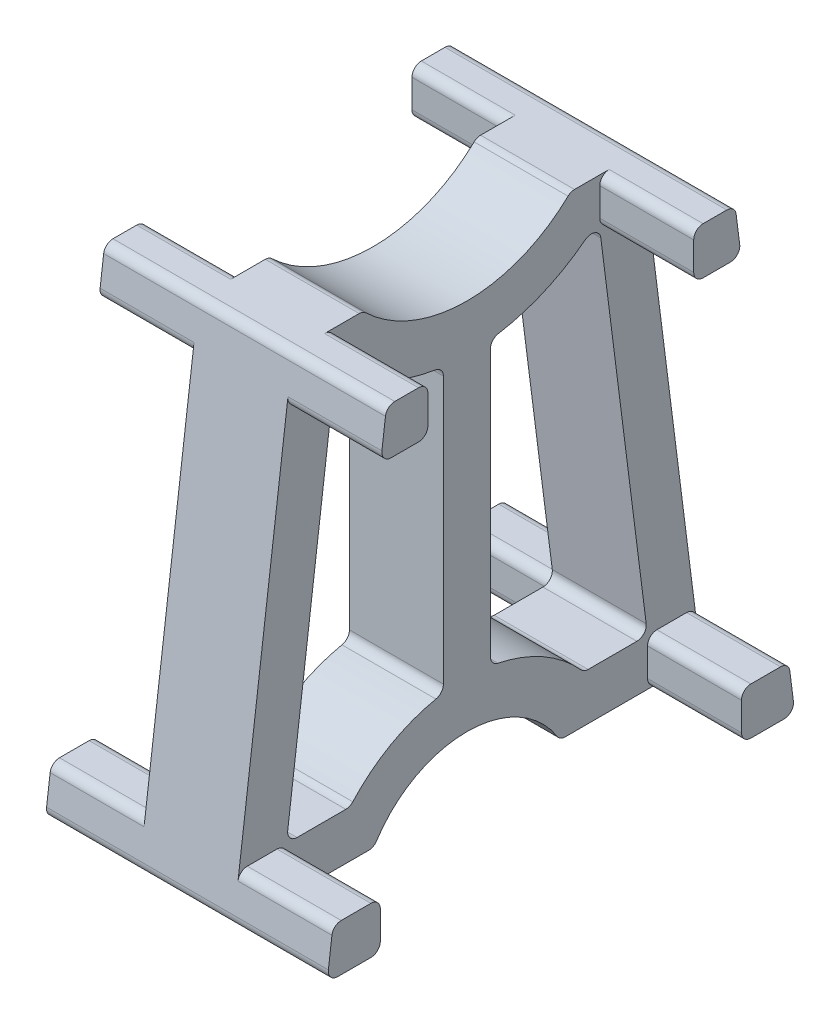
SolidWorks part; units mm, degrees
ref_plane "Front Plane" through (0, 0, 0) normal (0, 0, 1) x (1, 0, 0)
ref_plane "Top Plane" through (0, 0, 0) normal (0, 1, 0) x (1, 0, 0)
ref_plane "Right Plane" through (0, 0, 0) normal (1, 0, 0) x (0, 0, -1)
sketch "Sketch1" plane through (0, 0, 0) normal (1, 0, 0) x (0, 0, -1)
  line L0 (0, 0) -> (-28.1082, -28.1082) construction
  line L1 (0, 0) -> (28.1082, -28.1082) construction
  line L2 (0, 39.751) -> (0, -224.6171) construction
  line L3 (-28.1082, -28.1082) -> (-28.1082, -155.1082) construction
  line L4 (-25.1426, -155.1082) -> (0, -169.6243) construction
  line L5 (0, -169.6243) -> (25.1426, -155.1082) construction
  line L6 (-25.1426, -155.1082) -> (-63.2426, -155.1082)
  line L7 (25.1426, -155.1082) -> (63.2426, -155.1082)
  line L8 (-28.1082, -28.1082) -> (-47.1582, -28.1082)
  line L9 (28.0539, -28.1624) -> (47.1039, -28.1624)
  line L10 (-47.1582, -28.1082) -> (-63.2426, -155.1082)
  line L11 (47.1039, -28.1624) -> (63.2426, -155.1082)
  line L12 (-35.9652, -40.8082) -> (-48.8327, -142.4082)
  line L13 (-35.9652, -40.8082) -> (-32.7489, -40.8082)
  line L14 (-48.8327, -142.4082) -> (-31.6133, -142.4082)
  line L15 (35.9163, -40.8624) -> (48.8258, -142.4082)
  line L16 (48.8258, -142.4082) -> (31.6133, -142.4082)
  line L17 (35.9163, -40.8624) -> (32.6813, -40.8624)
  line L18 (0, -140.5921) -> (6.35, -140.5921) construction
  line L19 (0, -140.5921) -> (-6.35, -140.5921) construction
  line L20 (-0.0383, -39.751) -> (-6.3883, -39.751) construction
  line L21 (-0.0383, -39.751) -> (6.3117, -39.751) construction
  line L22 (-6.3799, -51.9336) -> (-6.375, -128.3996)
  line L23 (6.3535, -51.9368) -> (6.3584, -128.3971)
  circle A0 centre (0, 0) radius 39.751 construction
  circle A1 centre (0, -169.6243) radius 29.0322 construction
  arc A2 (-28.1082, -28.1082) -> (28.0539, -28.1624) centre (0, 0) ccw
  arc A3 (25.1426, -155.1082) -> (-25.1426, -155.1082) centre (0, -169.6243) ccw
  circle A4 centre (0, 0) radius 52.324 construction
  circle A5 centre (0, -169.6243) radius 41.7147 construction
  arc A6 (-31.6133, -142.4082) -> (-6.375, -128.3996) centre (0, -169.6243) cw
  arc A7 (31.6133, -142.4082) -> (6.3584, -128.3971) centre (0, -169.6243) ccw
  arc A8 (-32.7489, -40.8082) -> (-6.3799, -51.9336) centre (0, 0) ccw
  arc A9 (32.6813, -40.8624) -> (6.3535, -51.9368) centre (0, 0) cw
  dimension "D1" = 79.502
  dimension "D5" = 58.0644
  dimension "D10" = 104.648
  dimension "D11" = 12.7
  dimension "D2" = 45
  dimension "D3" = 45
  dimension "D4" = 127
  dimension "D6" = 60
  dimension "D7" = 60
  dimension "D8" = 38.1
  dimension "D9" = 19.05
  dimension "D12" = 12.7
  dimension "D13" = 12.7
  dimension "D14" = 12.7
  dimension "D15" = 12.7
  dimension "D16" = 12.7
  dimension "D17" = 6.35
extrude "Boss-Extrude1" add sketch "Sketch1" along normal blind 25.4 contours A3 L7 L11 L9 A2 L8 L10 L6 A9 L17 L15 L16 A7 L23 L13 A8 L22 A6 L14 L12 region at (0, -94.8563, 0.0179)
sketch "Sketch3" plane through (25.4, 0, 0) normal (1, 0, 0) x (0, 0, -1)
  line L0 (-48.8327, -142.4082) -> (-61.6342, -142.4082)
  line L1 (-47.1582, -28.1082) -> (-63.2426, -155.1082) construction
  line L2 (-61.6342, -142.4082) -> (-63.2426, -155.1082)
  line L3 (-63.2426, -155.1082) -> (-48.8327, -155.1082)
  line L4 (-25.1426, -155.1082) -> (-63.2426, -155.1082) construction
  line L5 (-48.8327, -155.1082) -> (-48.8327, -142.4082)
  line L6 (48.8258, -142.4082) -> (61.6281, -142.4082)
  line L7 (47.1039, -28.1624) -> (63.2426, -155.1082) construction
  line L8 (61.6281, -142.4082) -> (63.2426, -155.1082)
  line L9 (63.2426, -155.1082) -> (48.8258, -155.1082)
  line L10 (25.1426, -155.1082) -> (63.2426, -155.1082) construction
  line L11 (48.8258, -155.1082) -> (48.8258, -142.4082)
  line L12 (-35.9652, -40.8082) -> (-35.9652, -28.1082)
  line L13 (-28.1082, -28.1082) -> (-47.1582, -28.1082) construction
  line L14 (-35.9652, -28.1082) -> (-47.1582, -28.1082)
  line L15 (-47.1582, -28.1082) -> (-48.7666, -40.8082)
  line L16 (-48.7666, -40.8082) -> (-35.9652, -40.8082)
  line L17 (35.9163, -40.8624) -> (35.9163, -28.1624)
  line L18 (28.0539, -28.1624) -> (47.1039, -28.1624) construction
  line L19 (35.9163, -28.1624) -> (47.1039, -28.1624)
  line L20 (47.1039, -28.1624) -> (48.7185, -40.8624)
  line L21 (48.7185, -40.8624) -> (35.9163, -40.8624)
extrude "Boss-Extrude4" add sketch "Sketch3" along normal blind 25.4 and the other way blind 50.8
fillet "Fillet8" radius 2.54 12 edges at (12.7, -40.8082, 32.7489) (12.7, -128.3996, 6.375) (12.7, -142.4082, 48.8327) (12.7, -51.9336, 6.3799) (12.7, -40.8082, 35.9652) (12.7, -142.4082, -31.6133) (12.7, -142.4082, -48.8258) (12.7, -128.3971, -6.3584) (12.7, -51.9368, -6.3535) (12.7, -40.8624, -35.9163) (12.7, -40.8624, -32.6813) (12.7, -142.4082, 31.6133)
fillet "Fillet9" radius 2.54 14 edges at (-12.7, -28.1082, 35.9652) (-12.7, -40.8082, 48.7666) (-12.7, -40.8082, 35.9652) (38.1, -40.8082, 48.7666) (38.1, -40.8082, 35.9652) (12.7, -28.1082, 47.1582) (38.1, -28.1082, 35.9652) (38.1, -28.1624, -35.9163) (38.1, -40.8624, -35.9163) (38.1, -40.8624, -48.7185) (-12.7, -40.8624, -48.7185) (-12.7, -40.8624, -35.9163) (-12.7, -28.1624, -35.9163) (12.7, -28.1624, -47.1039)
fillet "Fillet10" radius 2.54 4 edges at (12.7, -28.1082, 28.1082) (12.7, -28.1624, -28.0539) (12.7, -155.1082, 25.1426) (12.7, -155.1082, -25.1426)
fillet "Fillet11" radius 2.54 14 edges at (38.1, -155.1082, 48.8327) (-12.7, -155.1082, 48.8327) (-12.7, -142.4082, 48.8327) (-12.7, -142.4082, 61.6342) (12.7, -155.1082, 63.2426) (38.1, -142.4082, 48.8327) (38.1, -142.4082, 61.6342) (38.1, -142.4082, -48.8258) (-12.7, -142.4082, -48.8258) (-12.7, -142.4082, -61.6281) (38.1, -142.4082, -61.6281) (38.1, -155.1082, -48.8258) (-12.7, -155.1082, -48.8258) (12.7, -155.1082, -63.2426)
sketch "Sketch4" plane through (0, 0, 0) normal (-1, 0, 0) x (0, 0, 1)
  line L0 (-28.0539, -28.1624) -> (-28.0539, -95.8466) construction
  line L1 (28.1082, -28.1082) -> (28.1082, -79.0933) construction
  line L2 (25.1426, -155.1082) -> (25.1426, -105.0931) construction
  line L3 (-25.1426, -155.1082) -> (-25.1426, -104.3384) construction
  arc A0 (-28.0539, -38.5737) -> (28.1082, -38.5342) centre (0, 0) ccw construction
  arc A1 (25.1426, -142.1976) -> (-25.1426, -142.1976) centre (0, -169.6243) ccw construction
  text T0 "<b>AIRFRAME</b>" font "Century Gothic" height in points 16
  text T1 "<b>MOTOR MOUNT TUBE</b>" font "Century Gothic" height in points 16
extrude "Cut-Extrude1" cut sketch "Sketch4" against normal blind 0.127
